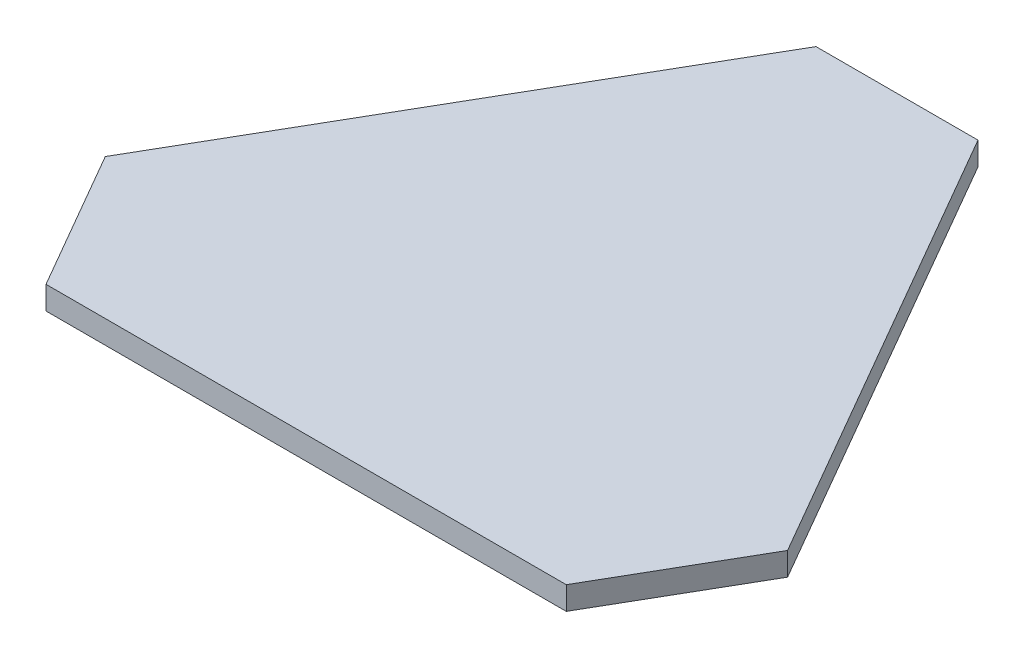
SolidWorks part; units mm, degrees
ref_plane "Front Plane" through (0, 0, 0) normal (0, 0, 1) x (1, 0, 0)
ref_plane "Top Plane" through (0, 0, 0) normal (0, 1, 0) x (1, 0, 0)
ref_plane "Right Plane" through (0, 0, 0) normal (1, 0, 0) x (0, 0, -1)
sketch "Sketch1" plane through (0, 0, 0) normal (0, 1, 0) x (1, 0, 0)
  line L0 (112.4038, -105.3109) -> (147.4038, -44.6891)
  line L1 (147.4038, -44.6891) -> (35, 150)
  line L2 (-35, 150) -> (-147.4038, -44.6891)
  line L3 (-112.4038, -105.3109) -> (112.4038, -105.3109)
  line L4 (-147.4038, -44.6891) -> (-112.4038, -105.3109)
  line L5 (35, 150) -> (-35, 150)
  circle A0 centre (0, 0) radius 105.3109 construction
  point P15 (0, 0)
  dimension "D1" = 150
  dimension "D2" = 70
  dimension "D4" = 3
extrude "Boss-Extrude1" add sketch "Sketch1" along normal blind 10
